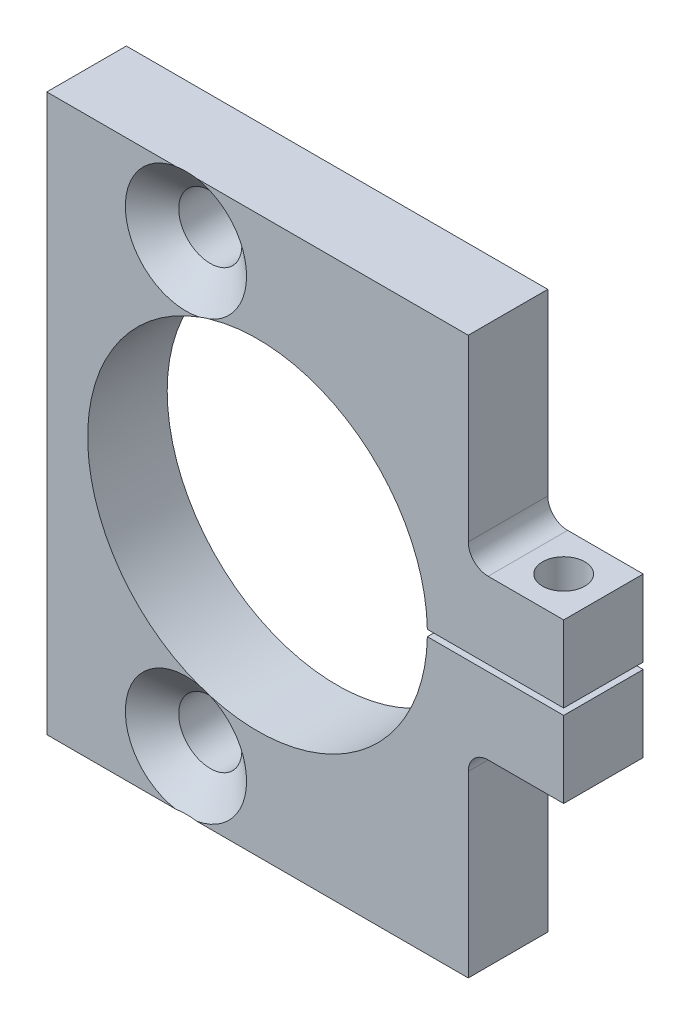
SolidWorks part; units mm, degrees
material "6061-T6 (SS)"
ref_plane "Front Plane" through (0, 0, 0) normal (0, 0, 1) x (1, 0, 0)
ref_plane "Top Plane" through (0, 0, 0) normal (0, 1, 0) x (1, 0, 0)
ref_plane "Right Plane" through (0, 0, 0) normal (1, 0, 0) x (0, 0, -1)
sketch "Sketch1" plane through (0, 0, 0) normal (0, 0, 1) x (1, 0, 0)
  line L1 (-41.275, -44.45) -> (41.275, -44.45)
  line L2 (-41.275, -44.45) -> (-41.275, 44.45)
  line L3 (-41.275, 44.45) -> (41.275, 44.45)
  line L4 (41.275, -44.45) -> (41.275, 44.45)
  line L5 (-41.275, -44.45) -> (41.275, 44.45) construction
  line L6 (-41.275, 44.45) -> (41.275, -44.45) construction
  point P0 (0, 0)
  dimension "D1" = 82.55
  dimension "D2" = 88.9
extrude "Extrude1" add sketch "Sketch1" along normal blind 12.7
sketch "Sketch2" plane through (0, 0, 12.7) normal (0, 0, 1) x (1, 0, 0)
  line L0 (-41.275, 0) -> (-7.62, 0) construction
  line L4 (-41.275, 44.45) -> (-41.275, -44.45) construction
  circle A0 centre (-7.62, 0) radius 27.1272
  dimension "D1" = 54.2544
  dimension "D2" = 33.655
extrude "Extrude2" cut sketch "Sketch2" against normal through all
sketch "Sketch3" plane through (0, 0, 12.7) normal (0, 0, 1) x (1, 0, 0)
  line L0 (19.5072, 0) -> (41.275, 0) construction
  line L1 (41.275, -44.45) -> (41.275, 44.45) construction
  line L3 (16.1568, -0.508) -> (44.6254, -0.508)
  line L4 (16.1568, -0.508) -> (16.1568, 0.508)
  line L5 (16.1568, 0.508) -> (44.6254, 0.508)
  line L6 (44.6254, -0.508) -> (44.6254, 0.508)
  line L7 (16.1568, -0.508) -> (44.6254, 0.508) construction
  line L8 (16.1568, 0.508) -> (44.6254, -0.508) construction
  circle A0 centre (-7.62, 0) radius 27.1272 construction
  point P6 (30.3911, 0)
  dimension "D1" = 1.016
extrude "Extrude3" cut sketch "Sketch3" against normal through all
sketch "Sketch4" plane through (0, 44.45, 0) normal (0, 1, 0) x (1, 0, 0)
  line L0 (41.275, -6.35) -> (34.925, -6.35) construction
  line L1 (41.275, -12.7) -> (41.275, 0) construction
  dimension "D1" = 6.35
hole_wizard "1/4 Clearance Hole1" positions "3DSketch1" profile "Sketch5" hole size "1/4" standard "Ansi Inch" end condition through all
sketch3d "3DSketch1"
  point P0 (34.925, 44.45, 6.35)
sketch "Sketch5" plane through (34.925, 44.45, 6.35) normal (1, 0, 0) x (0, 0, 1)
  line L0 (0, 0) -> (0, 88.9)
  line L1 (0, 88.9) -> (3.3782, 88.9)
  line L2 (3.3782, 88.9) -> (3.3782, 0)
  line L5 (3.3782, 0) -> (0, 0)
  line L11 (0, -6.35) -> (0, 107.95) construction
  dimension "Thru Hole Dia." = 6.7564
  dimension "Thru Hole Depth" = 88.9
sketch "Sketch8" plane through (0, 0, 12.7) normal (0, 0, 1) x (1, 0, 0)
  line L0 (-41.275, 34.925) -> (-19.05, 34.925) construction
  line L1 (-41.275, 44.45) -> (-41.275, -44.45) construction
  line L2 (41.275, 44.45) -> (-41.275, 44.45) construction
  dimension "D1" = 22.225
  dimension "D2" = 9.525
hole_wizard "CSK for 3/8 Flat Head Machine Screw (100)1" positions "3DSketch3" profile "Sketch9" countersink size "3/8" standard "Ansi Inch" end condition through all
sketch3d "3DSketch3"
  point P0 (-19.05, 34.925, 12.7)
sketch "Sketch9" plane through (-19.05, 34.925, 12.7) normal (1, 0, 0) x (0, -1, 0)
  line L0 (0, 0) -> (0, 12.7)
  line L1 (0, 12.7) -> (5.0419, 12.7)
  line L2 (5.0419, 12.7) -> (5.0419, 3.8896)
  line L3 (5.0419, 3.8896) -> (9.6774, 0)
  line L5 (9.6774, 0) -> (0, 0)
  line L6 (-5.0419, 3.8896) -> (-9.6774, 0) construction
  line L11 (0, -6.35) -> (0, 107.95) construction
  dimension "Thru Hole Dia." = 10.0838
  dimension "Thru Hole Depth" = 12.7
  dimension "Near C'Sink Dia." = 19.3548
  dimension "Near C'Sink Angle" = 100
mirror "Mirror1" about plane through (0, 0, 0) normal (0, 1, 0) of "CSK for 3/8 Flat Head Machine Screw (100)1"
sketch "Sketch10" plane through (0, 0, 12.7) normal (0, 0, 1) x (1, 0, 0)
  line L1 (41.275, 44.45) -> (26.035, 44.45)
  line L2 (41.275, 44.45) -> (41.275, 12.7)
  line L3 (41.275, 12.7) -> (26.035, 12.7)
  line L4 (26.035, 44.45) -> (26.035, 12.7)
  dimension "D1" = 15.24
  dimension "D2" = 31.75
extrude "Extrude4" cut sketch "Sketch10" against normal through all
mirror "Mirror2" about plane through (0, 0, 0) normal (0, 1, 0) of "Extrude4"
fillet "Fillet1" radius 3.175 2 edges at (26.035, -12.7, 6.35) (26.035, 12.7, 6.35)
ref_plane "Plane1" through (0, 0, 19.05) normal (0, 0, 1) x (1, 0, 0)
sketch "Sketch11" plane through (0, 0, 19.05) normal (0, 0, 1) x (1, 0, 0)
  point P0 (-41.275, -44.45)
